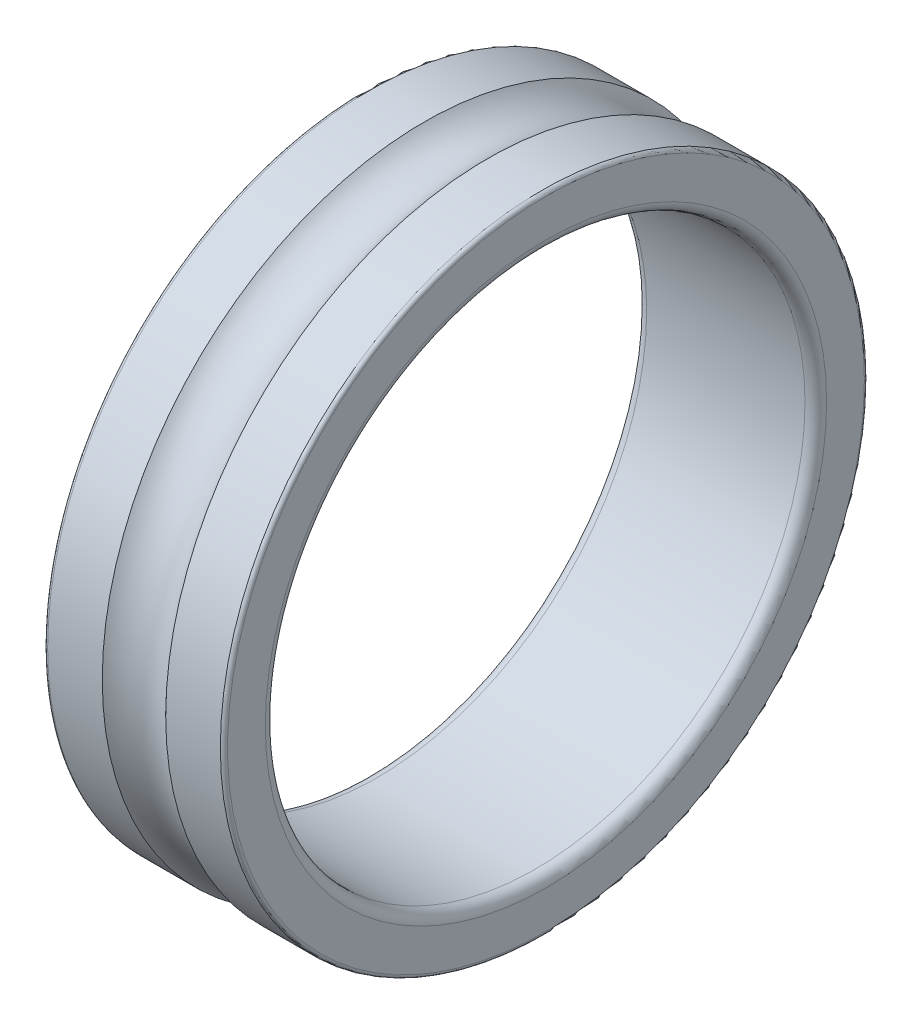
SolidWorks part; units mm, degrees
ref_plane "Front Plane" through (0, 0, 0) normal (0, 0, 1) x (1, 0, 0)
ref_plane "Top Plane" through (0, 0, 0) normal (0, 1, 0) x (1, 0, 0)
ref_plane "Right Plane" through (0, 0, 0) normal (1, 0, 0) x (0, 0, -1)
ref_plane "Plane1" through (0, 0, 0) normal (0, 0, 1) x (1, 0, 0)
sketch "Sketch1" plane through (0, 0, 0) normal (0, 0, 1) x (1, 0, 0)
  line L0 (0.3, 7.5) -> (4.7, 7.5)
  line L1 (5, 7.8) -> (5, 8.85)
  line L2 (4.9, 8.95) -> (3.3816, 8.95)
  line L3 (1.6184, 8.95) -> (0.1, 8.95)
  line L4 (0, 8.85) -> (0, 7.8)
  line L5 (4.7, 0) -> (0.3, 0) construction
  arc A0 (0, 7.8) -> (0.3, 7.5) centre (0.3, 7.8) ccw
  arc A1 (4.7, 7.5) -> (5, 7.8) centre (4.7, 7.8) ccw
  arc A2 (5, 8.85) -> (4.9, 8.95) centre (4.9, 8.85) ccw
  arc A3 (3.3816, 8.95) -> (1.6184, 8.95) centre (2.5, 9.75) cw
  arc A4 (0.1, 8.95) -> (0, 8.85) centre (0.1, 8.85) ccw
revolve "Revolve1" add sketch "Sketch1" angle 360 about L5
ref_axis "Axis1" through (0.3, 0, 0) along (1, 0, 0)
